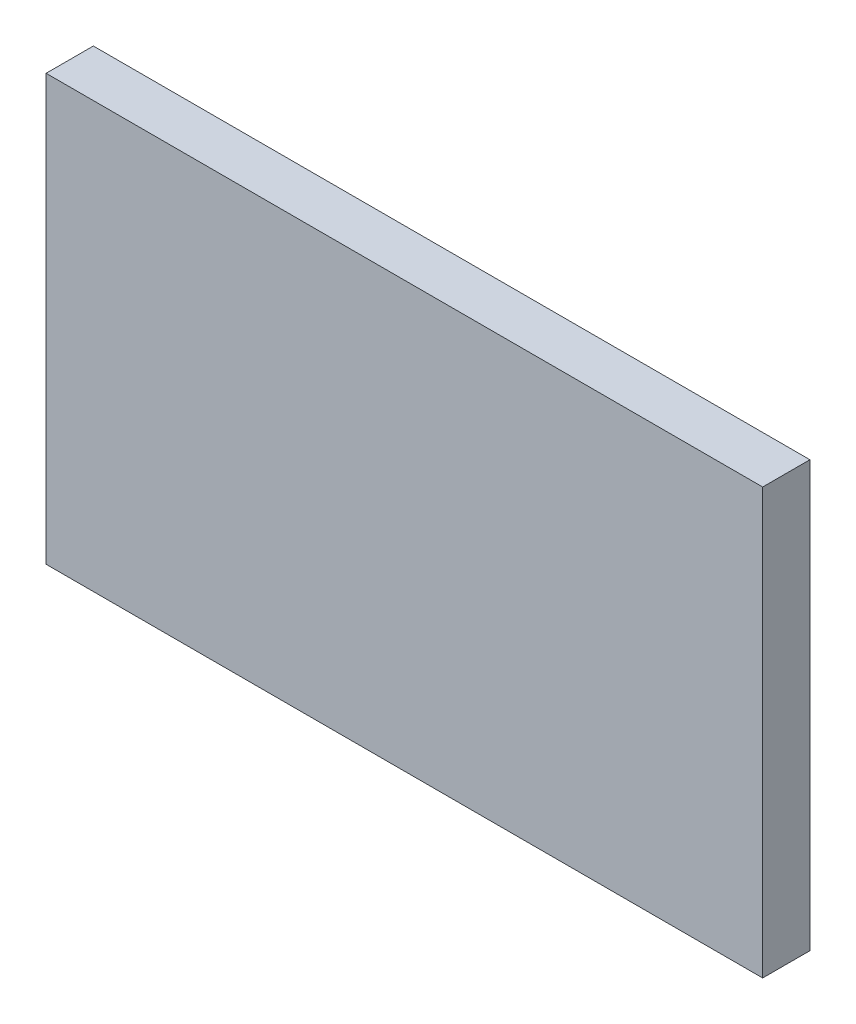
SolidWorks part; units mm, degrees
ref_plane "Front Plane" through (0, 0, 0) normal (0, 0, 1) x (1, 0, 0)
ref_plane "Top Plane" through (0, 0, 0) normal (0, 1, 0) x (1, 0, 0)
ref_plane "Right Plane" through (0, 0, 0) normal (1, 0, 0) x (0, 0, -1)
sketch "Sketch1" plane through (0, 0, 0) normal (0, 0, 1) x (1, 0, 0)
  line L1 (0, 0) -> (45.5, 0)
  line L2 (0, 0) -> (0, 27)
  line L3 (0, 27) -> (45.5, 27)
  line L4 (45.5, 0) -> (45.5, 27)
  dimension "D1" = 45.5
  dimension "D2" = 27
extrude "Boss-Extrude1" add sketch "Sketch1" along normal blind 3
